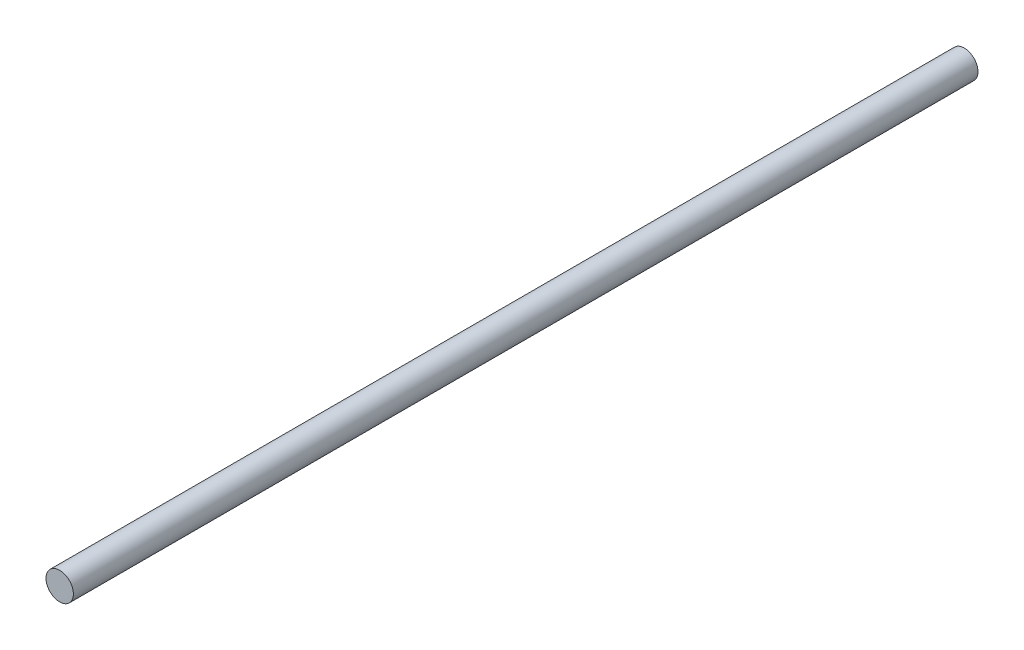
SolidWorks part; units mm, degrees
material "6061-T6 (SS)"
ref_plane "Front" through (0, 0, 0) normal (0, 0, 1) x (1, 0, 0)
ref_plane "Top" through (0, 0, 0) normal (0, 1, 0) x (1, 0, 0)
ref_plane "Right" through (0, 0, 0) normal (1, 0, 0) x (0, 0, -1)
sketch "Sketch1" plane through (0, 0, 0) normal (0, 0, 1) x (1, 0, 0)
  circle A0 centre (0, 0) radius 3.175
  dimension "D1" = 6.35
extrude "Boss-Extrude1" add sketch "Sketch1" along normal blind 209.55
